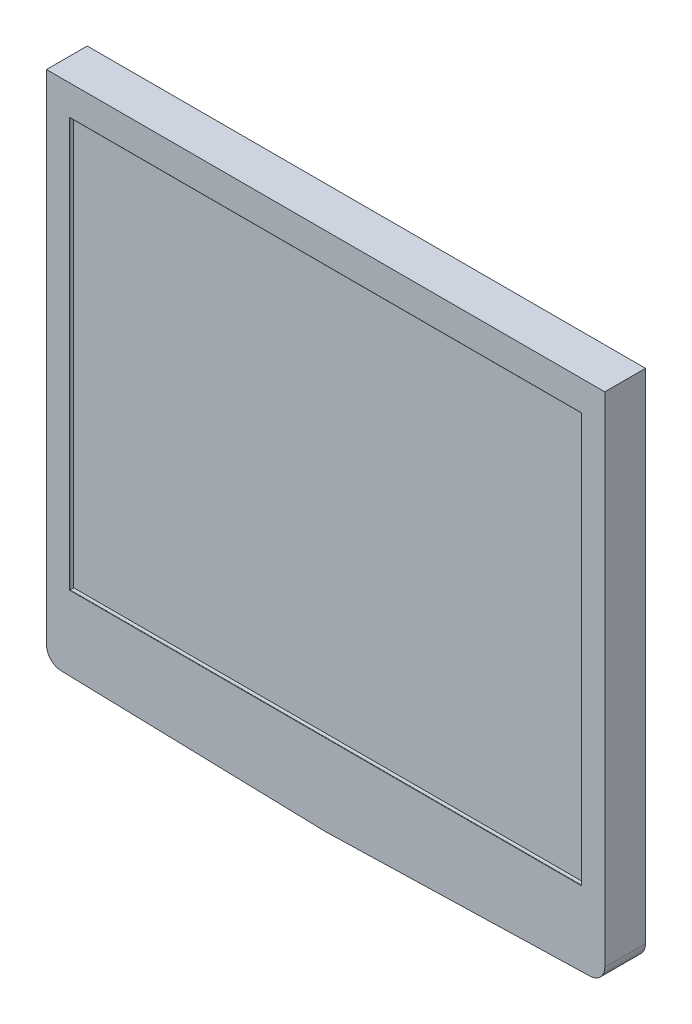
SolidWorks part; units mm, degrees
ref_plane "Front Plane" through (0, 0, 0) normal (0, 0, 1) x (1, 0, 0)
ref_plane "Top Plane" through (0, 0, 0) normal (0, 1, 0) x (1, 0, 0)
ref_plane "Right Plane" through (0, 0, 0) normal (1, 0, 0) x (0, 0, -1)
sketch "Sketch1" plane through (0, 0, 0) normal (0, 0, 1) x (1, 0, 0)
  line L0 (9.7298, -0.263) -> (184.7298, -4.9927)
  line L1 (185.2702, -4.9927) -> (360.2702, -0.263)
  line L2 (0, 9.7334) -> (0, 340)
  line L3 (0, 340) -> (370, 340)
  line L4 (370, 9.7334) -> (370, 340)
  arc A0 (184.7298, -4.9927) -> (185.2702, -4.9927) centre (185, 5.0037) ccw
  arc A1 (360.2702, -0.263) -> (370, 9.7334) centre (360, 9.7334) ccw
  arc A2 (9.7298, -0.263) -> (0, 9.7334) centre (10, 9.7334) cw
  point P8 (185, -5)
  point P11 (370, 0)
  point P14 (0, 0)
  dimension "D5" = 10
  dimension "D1" = 370
  dimension "D2" = 340
  dimension "D3" = 340
  dimension "D4" = 345
extrude "Boss-Extrude1" add sketch "Sketch1" along normal blind 27
sketch "Sketch2" plane through (0, 0, 27) normal (0, 0, 1) x (1, 0, 0)
  line L0 (0, 340) -> (0, 9.7334) construction
  line L1 (15.5, 320) -> (354.5, 320)
  line L2 (15.5, 320) -> (15.5, 49)
  line L3 (15.5, 49) -> (354.5, 49)
  line L4 (354.5, 320) -> (354.5, 49)
  line L5 (370, 340) -> (0, 340) construction
  dimension "D1" = 339
  dimension "D2" = 271
  dimension "D3" = 15.5
  dimension "D4" = 20
extrude "Cut-Extrude1" cut sketch "Sketch2" against normal blind 2.54
fillet "Fillet2" radius 0.254 4 edges at (354.5, 184.5, 24.46) (185, 49, 27) (15.5, 184.5, 27) (185, 320, 27)
sketch "Esquisse1" plane through (0, 0, 0) normal (0, 0, -1) x (-1, 0, 0)
  line L0 (-370, 9.7334) -> (-370, 340) construction
  line L1 (-342, 303) -> (-28, 303)
  line L2 (-342, 303) -> (-342, 7.0073)
  line L3 (-342, 7.0073) -> (-28, 7.0073)
  line L4 (-28, 303) -> (-28, 7.0073)
  line L5 (0, 340) -> (0, 9.7334) construction
  line L6 (-370, 340) -> (0, 340) construction
  dimension "D1" = 28
  dimension "D2" = 28
  dimension "D3" = 37
  dimension "D4" = 12
extrude "Boss.-Extru.1" add sketch "Esquisse1" along normal blind 25
chamfer "Chanfrein1" distance 25 distance2 35 3 edges at (28, 155.0037, -25) (185, 303, -25) (342, 155.0037, -25) first distance on face at (28, 155.0037, -12.5) first distance on face at (185, 303, -12.5) first distance on face at (342, 155.0037, -12.5)
sketch "Esquisse2" plane through (0, 0, -25) normal (0, 0, -1) x (-1, 0, 0)
  line L0 (-273.0633, 7.0073) -> (-89.8267, 7.0073)
  line L1 (-342, 7.0073) -> (-28, 7.0073) construction
  line L2 (-307, 7.0073) -> (-63, 7.0073) construction
  line L3 (-89.8267, 7.0073) -> (-89.8267, 60.0073)
  line L4 (-89.8267, 60.0073) -> (-66.8267, 60.0073)
  line L5 (-66.8267, 60.0073) -> (-66.8267, 108.0073)
  line L6 (-66.8267, 108.0073) -> (-296.0633, 108.0073)
  line L7 (-296.0633, 108.0073) -> (-296.0633, 60.0073)
  line L8 (-296.0633, 60.0073) -> (-273.0633, 60.0073)
  line L9 (-273.0633, 60.0073) -> (-273.0633, 7.0073)
  dimension "D1" = 23
  dimension "D2" = 23
  dimension "D3" = 53
  dimension "D4" = 53
  dimension "D5" = 48
extrude "Enlèv. mat.-Extru.1" cut sketch "Esquisse2" against normal blind 25
sketch "Esquisse3" plane through (0, 0, -25) normal (0, 0, -1) x (-1, 0, 0)
  line L0 (-63, 7.0073) -> (-63, 268) construction
  line L1 (-63, 268) -> (-307, 268) construction
  line L2 (-307, 268) -> (-307, 7.0073) construction
  circle A0 centre (-188, 255.8) radius 2.5
  circle A1 centre (-238, 193) radius 2.5
  circle A2 centre (-132, 193) radius 2.5
  dimension "D1" = 125
  dimension "D2" = 5
  dimension "D4" = 106
  dimension "D5" = 5
  dimension "D6" = 5
  dimension "D7" = 69
  dimension "D8" = 69
  dimension "D3" = 12.2
  dimension "D9" = 75
extrude "Enlèv. mat.-Extru.2" cut sketch "Esquisse3" against normal blind 15
